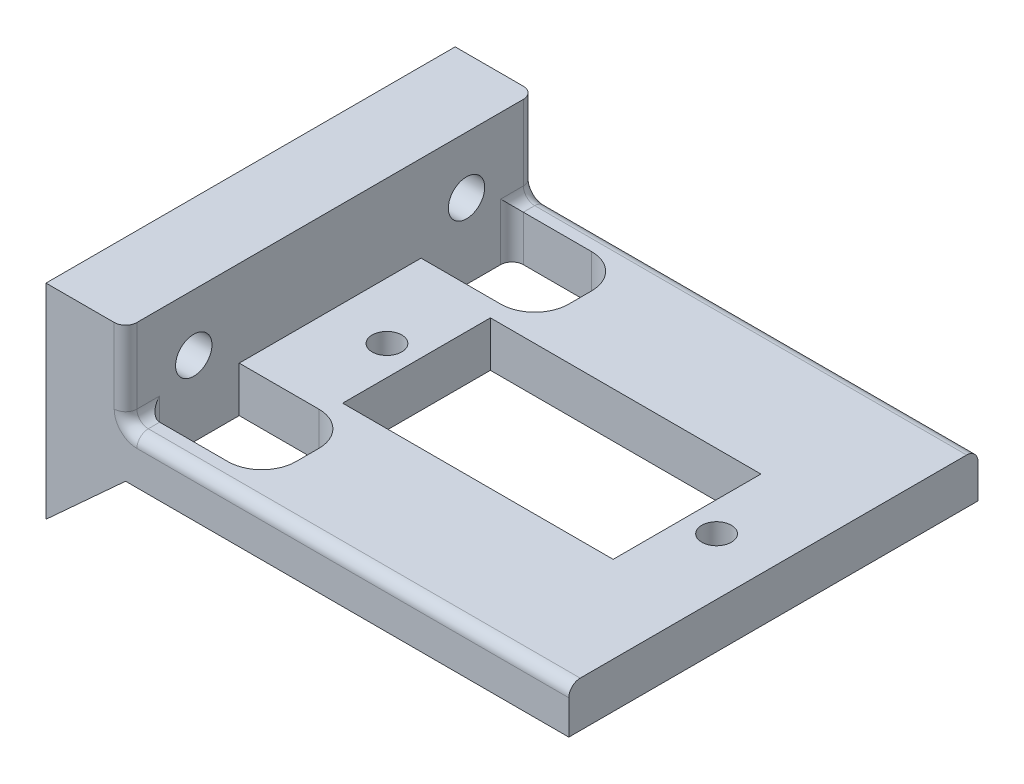
SolidWorks part; units mm, degrees
ref_plane "Front Plane" through (0, 0, 0) normal (0, 0, 1) x (1, 0, 0)
ref_plane "Top Plane" through (0, 0, 0) normal (0, 1, 0) x (1, 0, 0)
ref_plane "Right Plane" through (0, 0, 0) normal (1, 0, 0) x (0, 0, -1)
sketch "Servo_shelf_profile" plane through (0, 0, 0) normal (0, 1, 0) x (1, 0, 0)
  line L1 (-21, -18) -> (25, -18)
  line L2 (-21, -18) -> (-21, 18)
  line L3 (-21, 18) -> (25, 18)
  line L4 (25, -18) -> (25, 18)
  dimension "D1" = 46
  dimension "D2" = 36
  dimension "D3" = 25
  dimension "D4" = 18
extrude "Servo_shelf" add sketch "Servo_shelf_profile" along normal blind 4 from offset 21.4
sketch "Rear_clamping_block_profile" plane through (0, 0, 0) normal (0, 0, 1) x (1, 0, 0)
  line L1 (-21, 23) -> (-14, 23)
  line L2 (-21, 23) -> (-21, 33)
  line L3 (-21, 33) -> (-14, 33)
  line L4 (-14, 23) -> (-14, 33)
  dimension "D1" = 7
  dimension "D2" = 10
  dimension "D3" = 14
  dimension "D4" = 23
extrude "Rear_clamping_block" add sketch "Rear_clamping_block_profile" along normal blind 36 from offset 18 offset against normal yes
sketch "Servo_body_window_profile" plane through (0, 0, 0) normal (0, 1, 0) x (1, 0, 0)
  line L1 (-6.4, -6.5) -> (17.4, -6.5)
  line L2 (-6.4, -6.5) -> (-6.4, 6.5)
  line L3 (-6.4, 6.5) -> (17.4, 6.5)
  line L4 (17.4, -6.5) -> (17.4, 6.5)
  dimension "D1" = 23.8
  dimension "D2" = 13
  dimension "D3" = 17.4
  dimension "D4" = 6.5
extrude "Servo_body_window" cut sketch "Servo_body_window_profile" along normal through all from offset 20.4
sketch "Yaw_servo_M2_fasteners_profile" plane through (0, 0, 0) normal (0, 1, 0) x (1, 0, 0)
  circle A0 centre (-9, 0) radius 1.3
  circle A1 centre (20, 0) radius 1.3
  dimension "D1" = 2.6
  dimension "D2" = 2.6
  dimension "D3" = 20
  dimension "D4" = 9
extrude "Yaw_servo_M2_fasteners" cut sketch "Yaw_servo_M2_fasteners_profile" along normal through all from offset 20.4
sketch "Left_nut_access_profile" plane through (0, 0, 0) normal (0, 1, 0) x (1, 0, 0)
  line L1 (-14, 8) -> (-4, 8)
  line L2 (-14, 8) -> (-14, 16)
  line L3 (-14, 16) -> (-4, 16)
  line L4 (-4, 8) -> (-4, 16)
  dimension "D1" = 10
  dimension "D2" = 8
  dimension "D3" = 4
  dimension "D4" = 8
extrude "Left_nut_access" cut sketch "Left_nut_access_profile" along normal through all from offset 20
sketch "Right_nut_access_profile" plane through (0, 0, 0) normal (0, 1, 0) x (1, 0, 0)
  line L1 (-14, -16) -> (-4, -16)
  line L2 (-14, -16) -> (-14, -8)
  line L3 (-14, -8) -> (-4, -8)
  line L4 (-4, -16) -> (-4, -8)
  dimension "D1" = 10
  dimension "D2" = 8
  dimension "D3" = 4
  dimension "D4" = 8
extrude "Right_nut_access" cut sketch "Right_nut_access_profile" along normal through all from offset 20
sketch "Rear_clamping_M3_profile" plane through (0, 0, 0) normal (1, 0, 0) x (0, 0, -1)
  circle A0 centre (12, 28) radius 1.6
  circle A1 centre (-12, 28) radius 1.6
  dimension "D1" = 3.2
  dimension "D2" = 3.2
  dimension "D3" = 12
  dimension "D4" = 12
  dimension "D5" = 28
extrude "Rear_clamping_M3_holes" cut sketch "Rear_clamping_M3_profile" along normal blind 11 from offset 25 offset against normal yes
fillet "Fillet1" radius 3 4 edges at (-4, 23.4, 16) (-4, 23.4, 8) (-4, 23.4, -16) (-4, 23.4, -8)
fillet "Fillet2" radius 1 8 edges at (-14, 25.4, -17) (-14, 25.4, 17) (-14, 23.4, 16) (-14, 23.4, -16) (-14, 29.2, 18) (5.5, 25.4, 18) (-14, 29.2, -18) (5.5, 25.4, -18)
sketch "Sketch1" plane through (0, 0, -18) normal (0, 0, -1) x (-1, 0, 0)
  line L0 (14, 21.4) -> (21, 15)
  line L1 (21, 15) -> (21, 21.4)
  line L2 (21, 21.4) -> (14, 21.4)
extrude "Boss-Extrude1" add sketch "Sketch1" against normal up to surface (36 mm away) contours L0 L1 L2 up to face at (-5.0592, 26.2265, 18)
